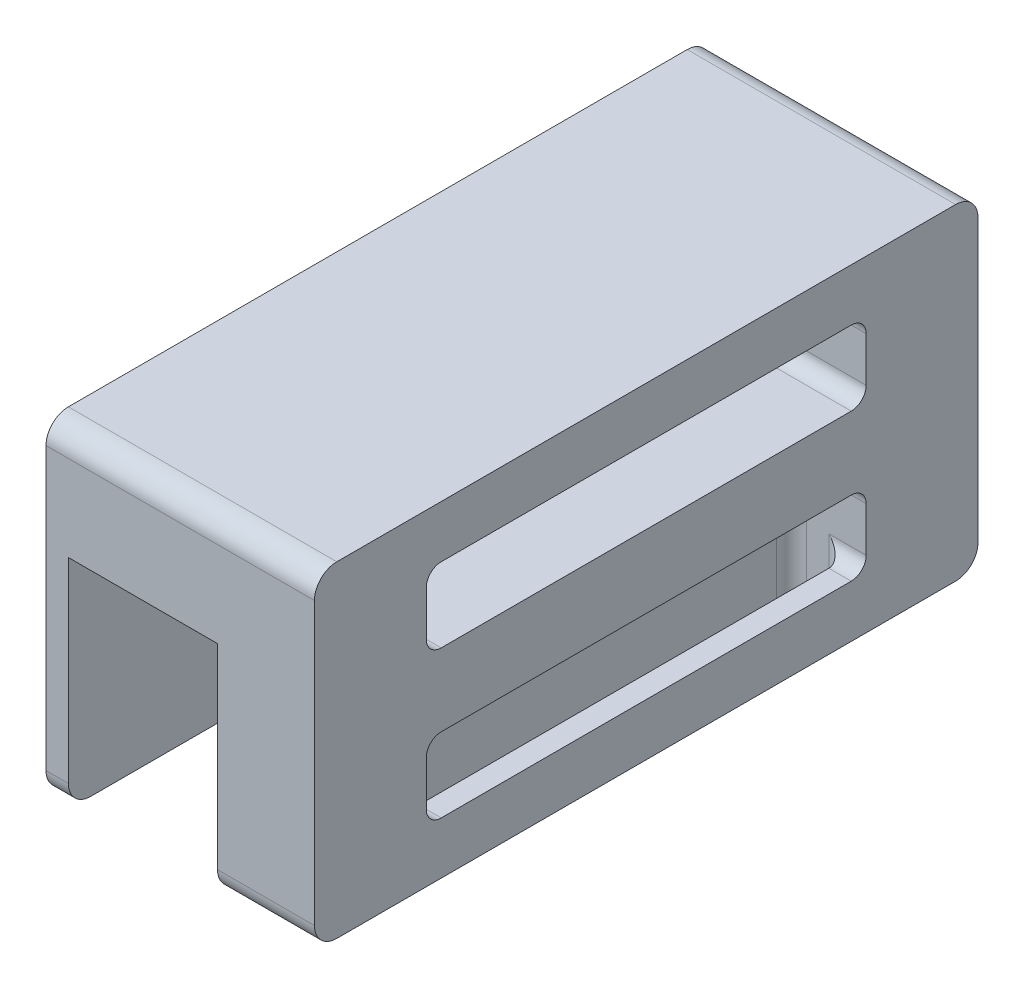
SolidWorks part; units mm, degrees
ref_plane "Plano frontal" through (0, 0, 0) normal (0, 0, 1) x (1, 0, 0)
ref_plane "Plano superior" through (0, 0, 0) normal (0, 1, 0) x (1, 0, 0)
ref_plane "Plano direito" through (0, 0, 0) normal (1, 0, 0) x (0, 0, -1)
sketch "Esboço2" plane through (0, 0, 0) normal (1, 0, 0) x (0, 0, -1)
  line L1 (2.9016, -0.0625) -> (-35.0984, -0.0625) construction
  line L2 (2.9016, -0.0625) -> (-35.0984, -0.0625)
  line L6 (7.6893, -0.0625) -> (2.9016, -0.0625)
  line L8 (-39.8861, -0.0625) -> (-35.0984, -0.0625)
  line L9 (-60.5984, 9.4769) -> (-60.5984, 20.9769)
  line L10 (28.4016, 9.4769) -> (28.4016, 20.9769)
  line L11 (-57.5984, 23.9769) -> (25.4016, 23.9769)
  arc A0 (28.4016, 20.9769) -> (25.4016, 23.9769) centre (25.4016, 20.9769) ccw
  arc A1 (-60.5984, 20.9769) -> (-57.5984, 23.9769) centre (-57.5984, 20.9769) cw
  arc A2 (28.4016, 9.4769) -> (24.5016, 12.3387) centre (25.4016, 9.4769) ccw
  arc A3 (-48.8914, 5.5897) -> (-56.6984, 12.3387) centre (-60.5984, -0.0625) ccw
  arc A4 (-48.8914, 5.5897) -> (-39.8861, -0.0625) centre (-39.8861, 9.9375) ccw
  arc A5 (-60.5984, 9.4769) -> (-56.6984, 12.3387) centre (-57.5984, 9.4769) cw
  arc A6 (16.6946, 5.5897) -> (7.6893, -0.0625) centre (7.6893, 9.9375) cw
  arc A7 (16.6946, 5.5897) -> (24.5016, 12.3387) centre (28.4016, -0.0625) cw
  point P22 (28.4016, 12.9375)
  point P23 (-60.5984, 12.9375)
  dimension "D1" = 3
extrude "Ressalto-extrusão2" add sketch "Esboço2" along normal blind 30
sketch "Esboço3" plane through (0, 0, 0) normal (-1, 0, 0) x (0, 0, 1)
  line L0 (60.5984, 15.2269) -> (60.5984, 20.9769)
  line L1 (60.5984, 20.9769) -> (60.5984, 9.4769) construction
  line L2 (-28.4016, 15.2269) -> (-28.4016, 20.9769)
  line L3 (-28.4016, 9.4769) -> (-28.4016, 20.9769) construction
  line L4 (16.0984, 23.9769) -> (57.5984, 23.9769)
  line L5 (-25.4016, 23.9769) -> (57.5984, 23.9769) construction
  line L6 (16.0984, 23.9769) -> (-25.4016, 23.9769)
  line L7 (60.5984, 15.2269) -> (60.5984, -16.7731)
  line L8 (-28.4016, 15.2269) -> (-28.4016, -16.7731)
  line L9 (57.5984, -19.7731) -> (-25.4016, -19.7731)
  arc A0 (57.5984, 23.9769) -> (60.5984, 20.9769) centre (57.5984, 20.9769) cw
  arc A1 (-28.4016, 20.9769) -> (-25.4016, 23.9769) centre (-25.4016, 20.9769) cw
  arc A2 (-28.4016, -16.7731) -> (-25.4016, -19.7731) centre (-25.4016, -16.7731) ccw
  arc A3 (60.5984, -16.7731) -> (57.5984, -19.7731) centre (57.5984, -16.7731) cw
  dimension "D1" = 3
  dimension "D2" = 3
extrude "Ressalto-extrusão3" add sketch "Esboço3" along normal blind 3
sketch "Esboço4" plane through (30, 0, 0) normal (1, 0, 0) x (0, 0, -1)
  line L0 (-16.0984, 23.9769) -> (25.4016, 23.9769)
  line L1 (25.4016, 23.9769) -> (-57.5984, 23.9769) construction
  line L2 (-16.0984, 23.9769) -> (-57.5984, 23.9769)
  line L3 (28.4016, 15.2269) -> (28.4016, 20.9769)
  line L4 (28.4016, 9.4769) -> (28.4016, 20.9769) construction
  line L5 (-60.5984, 20.9769) -> (-60.5984, 15.2269)
  line L7 (28.4016, 15.2269) -> (28.4016, -16.7731)
  line L8 (28.4016, 9.4769) -> (28.4016, -16.7731) construction
  line L9 (-60.5984, 20.9769) -> (-60.5984, 9.4769) construction
  line L10 (-60.5984, 15.2269) -> (-60.5984, -16.7731)
  line L11 (25.4016, -19.7731) -> (-57.5984, -19.7731)
  arc A0 (25.4016, 23.9769) -> (28.4016, 20.9769) centre (25.4016, 20.9769) cw
  arc A1 (-60.5984, 20.9769) -> (-57.5984, 23.9769) centre (-57.5984, 20.9769) cw
  arc A2 (-60.5984, -16.7731) -> (-57.5984, -19.7731) centre (-57.5984, -16.7731) ccw
  arc A3 (28.4016, -16.7731) -> (25.4016, -19.7731) centre (25.4016, -16.7731) cw
  point P23 (28.4016, -19.7731)
  dimension "D1" = 3
extrude "Ressalto-extrusão4" add sketch "Esboço4" along normal blind 3 and the other way blind 10
sketch "Esboço8" plane through (33, 0, 0) normal (1, 0, 0) x (0, 0, -1)
  line L0 (-60.5984, 20.9769) -> (-60.5984, -16.7731) construction
  line L1 (-43.5984, 16.9769) -> (11.4016, 16.9769)
  line L2 (-45.5984, 14.9769) -> (-45.5984, 8.9769)
  line L3 (-43.5984, 6.9769) -> (11.4016, 6.9769)
  line L4 (13.4016, 14.9769) -> (13.4016, 8.9769)
  line L5 (28.4016, -16.7731) -> (28.4016, 20.9769) construction
  line L6 (25.4016, 23.9769) -> (-57.5984, 23.9769) construction
  line L7 (-57.5984, -19.7731) -> (25.4016, -19.7731) construction
  line L8 (-43.5984, -2.7731) -> (11.4016, -2.7731)
  line L9 (-45.5984, -4.7731) -> (-45.5984, -10.7731)
  line L10 (-43.5984, -12.7731) -> (11.4016, -12.7731)
  line L11 (13.4016, -4.7731) -> (13.4016, -10.7731)
  arc A0 (-43.5984, 16.9769) -> (-45.5984, 14.9769) centre (-43.5984, 14.9769) ccw
  arc A1 (-45.5984, 8.9769) -> (-43.5984, 6.9769) centre (-43.5984, 8.9769) ccw
  arc A2 (11.4016, 16.9769) -> (13.4016, 14.9769) centre (11.4016, 14.9769) cw
  arc A3 (11.4016, 6.9769) -> (13.4016, 8.9769) centre (11.4016, 8.9769) ccw
  arc A4 (11.4016, -2.7731) -> (13.4016, -4.7731) centre (11.4016, -4.7731) cw
  arc A5 (11.4016, -12.7731) -> (13.4016, -10.7731) centre (11.4016, -10.7731) ccw
  arc A6 (-45.5984, -10.7731) -> (-43.5984, -12.7731) centre (-43.5984, -10.7731) ccw
  arc A7 (-43.5984, -2.7731) -> (-45.5984, -4.7731) centre (-43.5984, -4.7731) ccw
  arc A8 (11.4016, -2.7731) -> (13.4016, -4.7731) centre (11.4016, -4.7731) cw
  point P22 (13.4016, 16.9769)
  point P25 (13.4016, 6.9769)
  point P28 (13.4016, -2.7731)
  point P31 (13.4016, -12.7731)
  dimension "D9" = 2
  dimension "D10" = 2
  dimension "D1" = 15
  dimension "D2" = 15
  dimension "D3" = 7
  dimension "D4" = 10
  dimension "D5" = 15
  dimension "D6" = 15
  dimension "D7" = 7
  dimension "D8" = 10
extrude "Corte-extrusão1" cut sketch "Esboço8" against normal blind 10 contours L8 A7 L9 A6 L10 A5 L11 A4 | L3 A3 L4 A2 L1 A0 L2 A1 region at (33, 11.9769, 16.0984) region at (33, -7.7731, 16.0984)
sketch "Esboço9" plane through (0, -19.7731, 0) normal (0, -1, 0) x (-1, 0, 0)
  line L0 (-20, 28.4016) -> (-33, 28.4016) construction
  line L1 (-25, 13.4016) -> (-28, 13.4016)
  line L2 (-23, 11.4016) -> (-23, -43.5984)
  line L3 (-25, -45.5984) -> (-28, -45.5984)
  line L4 (-30, 11.4016) -> (-30, -43.5984)
  line L5 (-20, -60.5984) -> (-33, -60.5984) construction
  line L6 (-33, -57.5984) -> (-33, 25.4016) construction
  line L7 (-20, -57.5984) -> (-20, 25.4016) construction
  arc A0 (-28, -45.5984) -> (-30, -43.5984) centre (-28, -43.5984) cw
  arc A1 (-23, -43.5984) -> (-25, -45.5984) centre (-25, -43.5984) cw
  arc A2 (-28, 13.4016) -> (-30, 11.4016) centre (-28, 11.4016) ccw
  arc A3 (-25, 13.4016) -> (-23, 11.4016) centre (-25, 11.4016) cw
  dimension "D5" = 2
  dimension "D1" = 15
  dimension "D2" = 15
  dimension "D3" = 3
  dimension "D4" = 3
extrude "Corte-extrusão2" cut sketch "Esboço9" against normal up to next
fillet "Filete1" radius 2 5 edges at (23, -7.7731, 45.5984) (23, -3.3589, 45.0126) (23, -2.7731, 16.0984) (23, -3.3589, -12.8158) (23, -7.7731, -13.4016)
